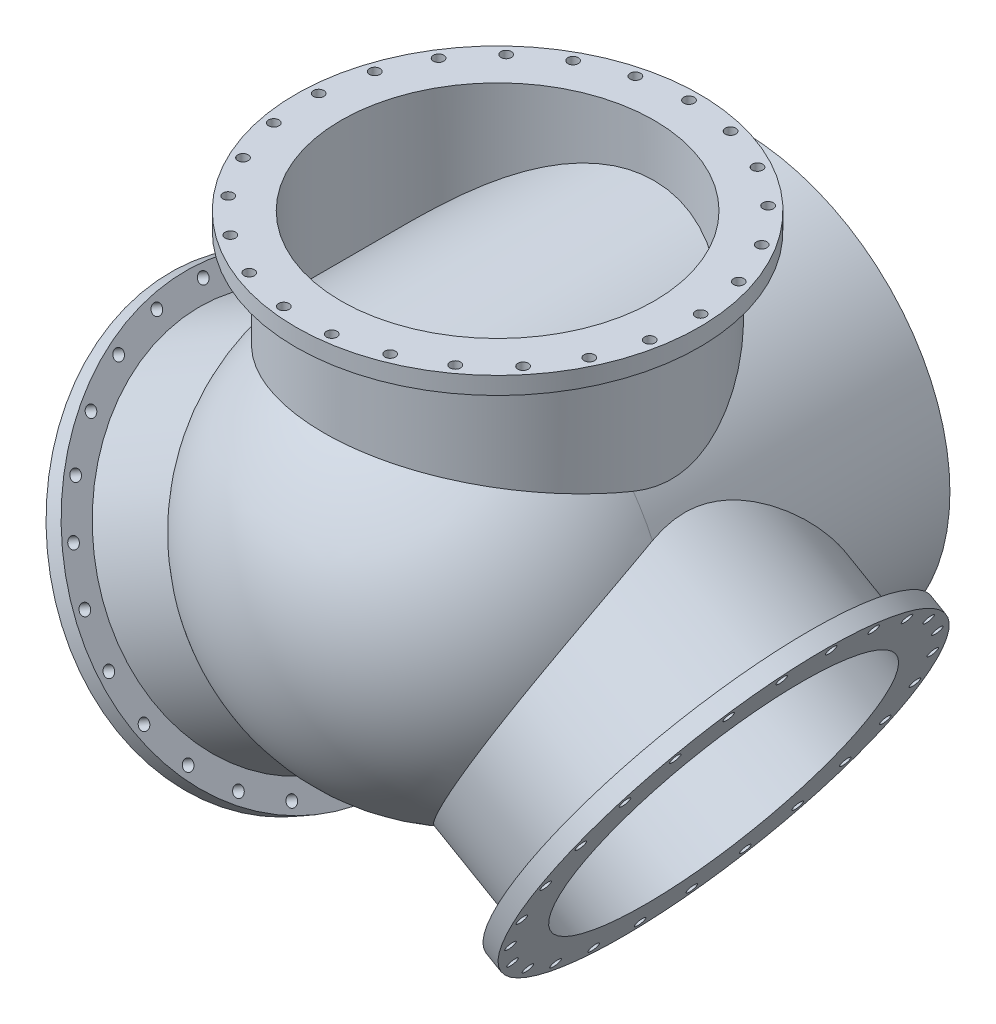
SolidWorks part; units mm, degrees
ref_plane "Ebene vorne" through (0, 0, 0) normal (0, 0, 1) x (1, 0, 0)
ref_plane "Ebene oben" through (0, 0, 0) normal (0, 1, 0) x (1, 0, 0)
ref_plane "Ebene rechts" through (0, 0, 0) normal (1, 0, 0) x (0, 0, -1)
sketch "Skizze1" plane through (0, 0, 0) normal (0, 0, 1) x (1, 0, 0)
  circle A0 centre (0, 0) radius 2400
extrude "Aufsatz-Linear austragen1" add sketch "Skizze1" along normal blind 2800 and the other way blind 2800
sketch "Skizze2" plane through (0, 0, 0) normal (0, 1, 0) x (1, 0, 0)
  circle A0 centre (0, 0) radius 2000
  circle A1 centre (0, 0) radius 1800
extrude "Aufsatz-Linear austragen2" add sketch "Skizze2" along normal blind 3000
sketch "Skizze3" plane through (0, 0, 0) normal (0, 1, 0) x (1, 0, 0)
  circle A0 centre (0, 0) radius 2320
  circle A1 centre (0, 0) radius 1800
extrude "Aufsatz-Linear austragen3" add sketch "Skizze3" along normal blind 200 from offset 2800
sketch "Skizze4" plane through (0, 3000, 0) normal (0, 1, 0) x (1, 0, 0)
  circle A0 centre (0, 2200) radius 60
  circle A1 centre (547.1178, 2130.883) radius 60
  circle A2 centre (1059.8581, 1927.8747) radius 60
  circle A3 centre (1506.0036, 1603.731) radius 60
  circle A4 centre (1857.5214, 1178.8189) radius 60
  circle A5 centre (2092.3243, 679.8374) radius 60
  circle A6 centre (2195.6588, 138.1391) radius 60
  circle A7 centre (2161.032, -412.2389) radius 60
  circle A8 centre (1990.6195, -936.7144) radius 60
  circle A9 centre (1695.1291, -1402.3328) radius 60
  circle A10 centre (1293.1276, -1779.8374) radius 60
  circle A11 centre (809.874, -2045.5083) radius 60
  circle A12 centre (275.7331, -2182.6523) radius 60
  circle A13 centre (-275.7331, -2182.6523) radius 60
  circle A14 centre (-809.874, -2045.5083) radius 60
  circle A15 centre (-1293.1276, -1779.8374) radius 60
  circle A16 centre (-1695.1291, -1402.3328) radius 60
  circle A17 centre (-1990.6195, -936.7144) radius 60
  circle A18 centre (-2161.032, -412.2389) radius 60
  circle A19 centre (-2195.6588, 138.1391) radius 60
  circle A20 centre (-2092.3243, 679.8374) radius 60
  circle A21 centre (-1857.5214, 1178.8189) radius 60
  circle A22 centre (-1506.0036, 1603.731) radius 60
  circle A23 centre (-1059.8581, 1927.8747) radius 60
  circle A24 centre (-547.1178, 2130.883) radius 60
  point P50 (0, 0)
  dimension "D1" = 25
extrude "Schnitt-Linear austragen1" cut sketch "Skizze4" against normal up to next (200 mm away)
pattern_circular "Kreismuster1" count 3 over 360 about axis through (0, 0, -2800) along (0, 0, -1) of "Aufsatz-Linear austragen2" reverse direction yes
pattern_circular "Kreismuster2" count 3 over 360 about axis through (0, 0, -2800) along (0, 0, -1) of "Aufsatz-Linear austragen3", "Schnitt-Linear austragen1" reverse direction yes
fillet "Verrundung1" radius 2400 1 edges at (2400, 0, 2800)
